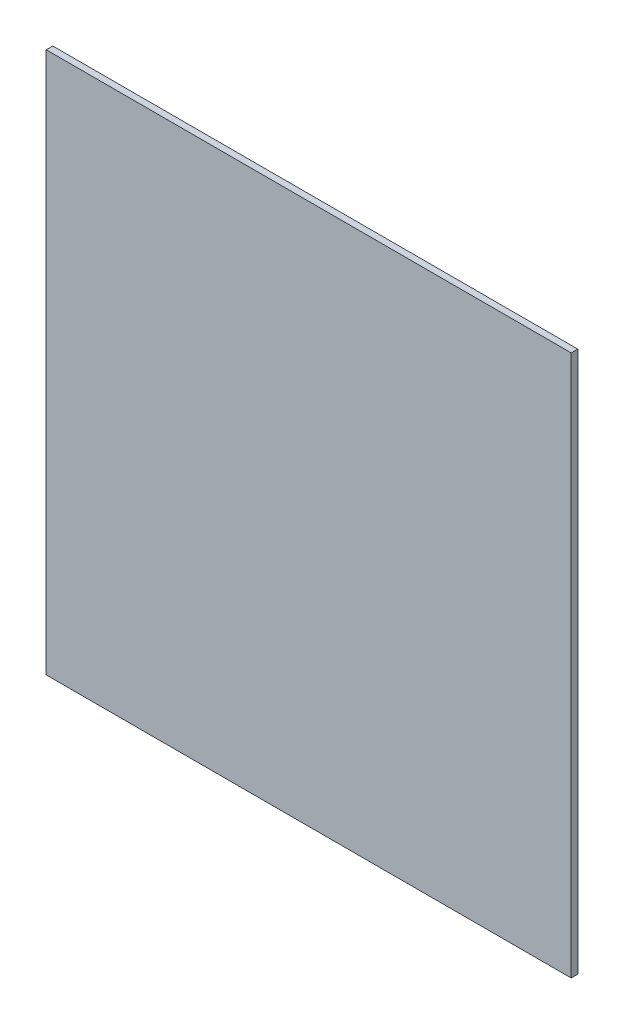
SolidWorks part; units mm, degrees
material "6061-T6 (SS)"
ref_plane "Front Plane" through (0, 0, 0) normal (0, 0, 1) x (1, 0, 0)
ref_plane "Top Plane" through (0, 0, 0) normal (0, 1, 0) x (1, 0, 0)
ref_plane "Right Plane" through (0, 0, 0) normal (1, 0, 0) x (0, 0, -1)
sketch "Sketch2" plane through (0, 0, 0) normal (0, 0, 1) x (1, 0, 0)
  line L1 (-160, 160) -> (160, 160)
  line L2 (-160, 160) -> (-160, -170)
  line L3 (-160, -170) -> (160, -170)
  line L4 (160, 160) -> (160, -170)
  dimension "D1" = 320
  dimension "D2" = 330
  dimension "D3" = 160
  dimension "D4" = 160
extrude "Boss-Extrude2" add sketch "Sketch2" along normal blind 4
